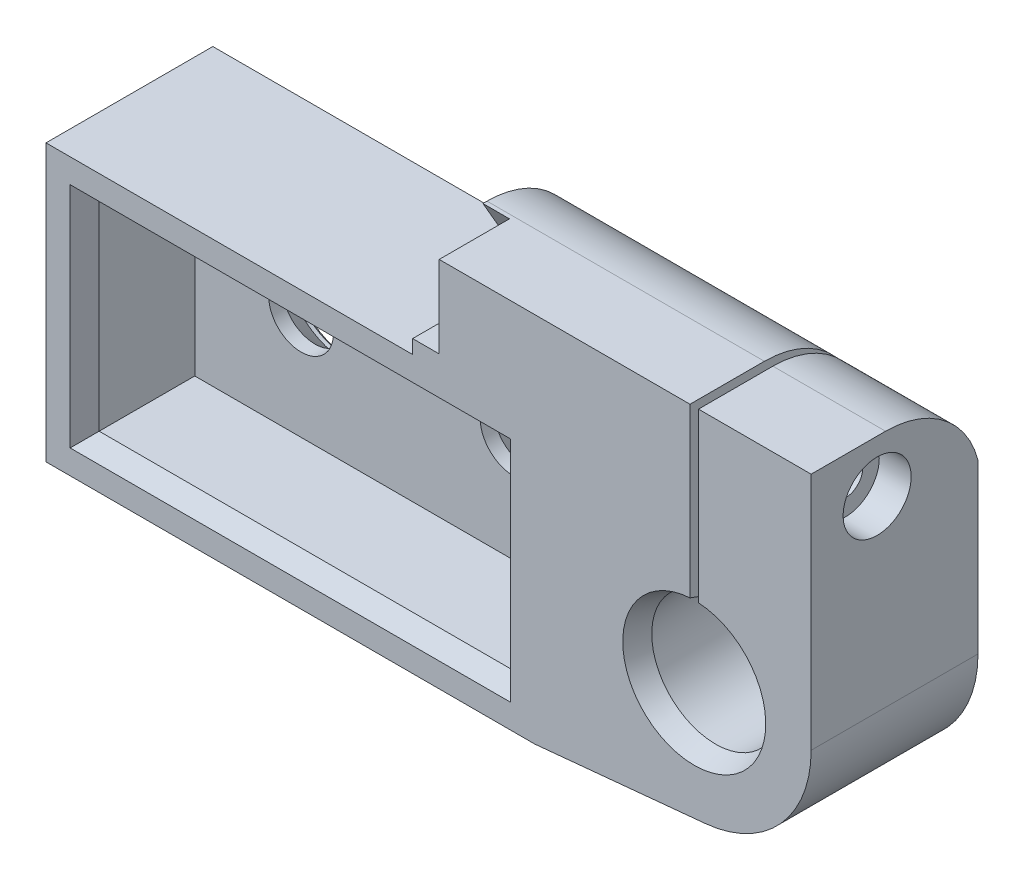
SolidWorks part; units mm, degrees
material "Custom Plastic"
ref_plane "Front Plane" through (0, 0, 0) normal (0, 0, 1) x (1, 0, 0)
ref_plane "Top Plane" through (0, 0, 0) normal (0, 1, 0) x (1, 0, 0)
ref_plane "Right Plane" through (0, 0, 0) normal (1, 0, 0) x (0, 0, -1)
sketch "Sketch1" plane through (0, 0, 0) normal (0, 0, 1) x (1, 0, 0)
  line L0 (-58, 10.5) -> (-18, -9.5) construction
  line L1 (-18, 10.5) -> (-58, 10.5) construction
  line L2 (-18, 10.5) -> (-18, -9.5) construction
  line L3 (-18, -9.5) -> (-58, -9.5) construction
  line L4 (-58, 10.5) -> (-58, -9.5) construction
  line L5 (-58, -9.5) -> (-18, 10.5) construction
  line L6 (-61, 13.5) -> (-61, -12.5)
  line L7 (-15, 13.5) -> (-61, 13.5) construction
  line L8 (-15, 13.5) -> (1.7126, 10.8659) construction
  line L10 (-48, 0.5) -> (-28, 0.5) construction
  line L11 (-61, -12.5) -> (-15, -12.5)
  line L12 (-15, -12.5) -> (-61, -12.5) construction
  line L13 (-15, 13.5) -> (-15, -12.5) construction
  line L14 (-15, -12.5) -> (1.0575, -10.949)
  line L15 (11, 0) -> (11, 22.5)
  line L16 (11, 22.5) -> (-26.5, 22.5)
  line L17 (-61, 13.5) -> (-26.5, 13.5)
  line L18 (-26.5, 13.5) -> (-26.5, 22.5)
  circle A0 centre (0, 0) radius 6 construction
  arc A1 (1.0575, -10.949) -> (11, 0) centre (0, 0) ccw
  circle A2 centre (-48, 0.5) radius 2.5
  circle A3 centre (-28, 0.5) radius 3.15
  point P11 (0, 0)
  point P12 (-38, 0.5)
  point P13 (9.6881, 0)
  dimension "D3" = 12
  dimension "D4" = 5
  dimension "D8" = 5
  dimension "D10" = 6.3
  dimension "D2" = 20
  dimension "D5" = 38
  dimension "D6" = 0.5
  dimension "D7" = 40
  dimension "D9" = 20
  dimension "D11" = 9
  dimension "D12" = 37.5
  dimension "D1" = 3
extrude "Boss-Extrude1" add sketch "Sketch1" along normal blind 16
sketch "Sketch2" plane through (0, 0, 16) normal (0, 0, 1) x (1, 0, 0)
  line L0 (-61, 13.5) -> (-61, -12.5) construction
  line L1 (-58, 10.5) -> (-18, 10.5)
  line L2 (-58, 10.5) -> (-58, -9.5)
  line L3 (-58, -9.5) -> (-18, -9.5)
  line L4 (-18, 10.5) -> (-18, -9.5)
  line L6 (-61, -12.5) -> (-15, -12.5) construction
  dimension "D1" = 3
  dimension "D2" = 3
  dimension "D3" = 20
  dimension "D4" = 40
extrude "Cut-Extrude1" cut sketch "Sketch2" against normal offset from surface (11 mm away) 5 up to face at (-20.6035, 4.2663, 0)
fillet "Fillet2" radius 9 1 edges at (-7.75, 22.5, 0)
sketch "Sketch3" plane through (0, 0, 16) normal (0, 0, 1) x (1, 0, 0)
  circle A0 centre (0, 0) radius 6
  dimension "D1" = 12
extrude "Cut-Extrude2" cut sketch "Sketch3" against normal offset from surface (13.5 mm away) 2.5 up to face at (-19.7611, 0.3758, 0)
sketch "Sketch6" plane through (0, 0, 16) normal (0, 0, 1) x (1, 0, 0)
  line L9 (-0.4, 24.3347) -> (0.4, 24.3347)
  line L10 (-0.4, 24.3347) -> (-0.4, 2.9732)
  line L15 (0.4, 24.3347) -> (0.4, 2.9732)
  line L16 (-0.4, 24.3347) -> (0.4, 2.9732) construction
  line L17 (-0.4, 2.9732) -> (0.4, 24.3347) construction
  arc A1 (-0.4, 2.9732) -> (0.4, 2.9732) centre (0, 0) ccw
  point P3 (0.1507, 0.3705)
  point P6 (0, 13.6539)
  point P7 (-14.5521, 6.3495)
  point P9 (-0.1507, -0.3705)
  point P10 (-15.3521, 5.8112)
  dimension "D4" = 3
  dimension "D3" = 0.8
extrude "Cut-Extrude5" cut sketch "Sketch6" against normal through all
sketch "Sketch7" plane through (0, 0, 0) normal (0, 0, -1) x (-1, 0, 0)
  line L0 (38, 10.5) -> (58, -9.5) construction
  line L1 (58, 10.5) -> (48, 0.5) construction
  line L3 (58, 10.5) -> (18, 10.5) construction
  circle A0 centre (48, 0.5) radius 3.05
  dimension "D1" = 6.1
extrude "Cut-Extrude6" cut sketch "Sketch7" against normal through all
sketch "Sketch8" plane through (0, 0, 16) normal (0, 0, 1) x (1, 0, 0)
  line L0 (-51.5, 9.5) -> (-44.5, 9.5) construction
  line L1 (-48, 9.5) -> (-48, 0.5) construction
  line L2 (-58, 10.5) -> (-18, 10.5) construction
  line L3 (-18, 10.5) -> (-58, 10.5) construction
  line L4 (-48, 12.2222) -> (-51.8111, 8.4111)
  line L5 (-51.8111, 8.4111) -> (-48, 4.6)
  line L6 (-48, 4.6) -> (-44.1889, 8.4111)
  line L7 (-44.1889, 8.4111) -> (-48, 12.2222)
  circle A0 centre (-51.5, 9.5) radius 0.55 construction
  circle A1 centre (-44.5, 9.5) radius 0.55 construction
  circle A2 centre (-48, 8.4111) radius 2.6948 construction
  dimension "D1" = 1.1
  dimension "D2" = 7
  dimension "D3" = 1
  dimension "D4" = 5.9
extrude "Boss-Extrude2" [suppressed] add sketch "Sketch8" against normal up to next
ref_axis "Axis1" through (-48, 0.5, 5) along (0, 0, -1)
pattern_circular "CirPattern1" [suppressed] count 2 over 360 about axis through (-48, 0.5, 5) along (0, 0, -1) of bodies 108
fillet "Fillet1" [suppressed] radius 0.8
chamfer "Chamfer2" distance 2 angle 20 4 edges at (-18, 0.5, 16) (-38, 10.5, 16) (-58, 0.5, 16) (-38, -9.5, 16) first distance on face at (-18, 0.5, 10.5) first distance on face at (-38, 10.5, 10.5) first distance on face at (-58, 0.5, 10.5) first distance on face at (-38, -9.5, 10.5)
sketch "Sketch10" plane through (0, 0, 0) normal (0, 0, -1) x (-1, 0, 0)
  circle A0 centre (28, 0.5) radius 6.1
  circle A1 centre (48, 0.5) radius 6.1
  dimension "D1" = 12.2
extrude "Cut-Extrude8" cut sketch "Sketch10" against normal blind 0.7
chamfer "Chamfer3" distance 3 angle 45 2 edges at (-51.05, 0.5, 0.7) (-31.15, 0.5, 0.7)
chamfer "Chamfer4" distance 0.3 angle 45 11 edges at (0, -3, 0) (-61, 0.5, 0) (-38, -12.5, 0) (-6.9712, -11.7245, 0) (8.1435, -7.3948, 0) (-34.1, 0.5, 0) (-54.1, 0.5, 0) (0.4, 8.2366, 0) (-0.4, 8.2366, 0) (11, 6.75, 0) (-43.75, 13.5, 0) tangent propagation no
sketch "Sketch11" plane through (11, 0, 0) normal (1, 0, 0) x (0, 0, -1)
  line L1 (-16, 13.5) -> (-0.3, 13.5) construction
  circle A0 centre (-9.7903, 17.6) radius 1.65
  circle A1 centre (-9.7903, 17.6) radius 3.1 construction
  point P3 (-9.7903, 14.5)
  dimension "D1" = 3.3
  dimension "D2" = 6.2
  dimension "D3" = 1
extrude "Cut-Extrude9" cut sketch "Sketch11" against normal through all
sketch "Sketch12" plane through (11, 0, 0) normal (1, 0, 0) x (0, 0, -1)
  circle A0 centre (-9.7903, 17.6) radius 3.2
  dimension "D1" = 6.4
extrude "Cut-Extrude10" cut sketch "Sketch12" against normal blind 3
sketch "Sketch13" plane through (11, 0, 0) normal (1, 0, 0) x (0, 0, -1)
  line L0 (-9.3862, 22.5) -> (-16, 22.5)
  line L1 (-6.5571, 17.6) -> (-9.3862, 22.5)
  line L2 (-8.2925, 20.4) -> (-11.4069, 20.4) construction
  line L3 (-11.4069, 20.4) -> (-13.0235, 17.6) construction
  line L4 (-13.0235, 17.6) -> (-11.3764, 14.7471) construction
  line L5 (-16, 14.8) -> (-8.1737, 14.8)
  line L6 (-8.1737, 14.8) -> (-6.5571, 17.6)
  line L8 (-16, 22.5) -> (-16, 14.8)
  line L10 (-16, 0) -> (-16, 22.5) construction
  line L11 (-16, 22.5) -> (-9, 22.5) construction
  circle A0 centre (-9.7903, 17.6) radius 2.8 construction
  dimension "D1" = 5.6
extrude "Cut-Extrude11" cut sketch "Sketch13" against normal through all from offset 35 offset against normal yes
chamfer "Chamfer5" distance 2 angle 20 1 edges at (0, -6, 16) first distance on face at (0, -0.0067, 9.25)
sketch "Sketch14" plane through (11, 0, 0) normal (1, 0, 0) x (0, 0, -1)
  line L0 (-9.7903, 17.6) -> (-10.957, 18.7667)
  line L1 (-10.957, 18.7667) -> (-11.7603, 17.9635)
  line L2 (-11.7603, 17.9635) -> (-11.7603, 17.2365)
  line L3 (-11.7603, 17.2365) -> (-10.957, 16.4333)
  line L4 (-10.957, 16.4333) -> (-9.7903, 17.6)
  circle A0 centre (-9.7903, 17.6) radius 1.65 construction
  point P8 (-11.4403, 17.6)
  dimension "D1" = 0.32
extrude "Cut-Extrude12" cut sketch "Sketch14" against normal through all
equation "\"y-cross-rib-thickness\"=6"
equation "\"y-rib-thickness\"=6"
equation "\"bed-plate-thickness\"=6"
equation "\"x-plate-thickness\"=5"
equation "\"rod-diameter\"=12"
equation "\"t-nut-hole-diameter\"=3"
equation "\"y-plate-thickness\"=5"
equation "\"enclosure-thickness\"=0.6"
equation "\"M3-Clearance\"=3.3"
equation "\"M4-Clearance\"=4.3"
equation "\"M5-Clearance\"=5.3"
equation "\"M6-Clearance\"=6.3"
equation "\"M8-Clearance\"=8.3"
equation "\"623-Bearing-Dia\"=11.2"
